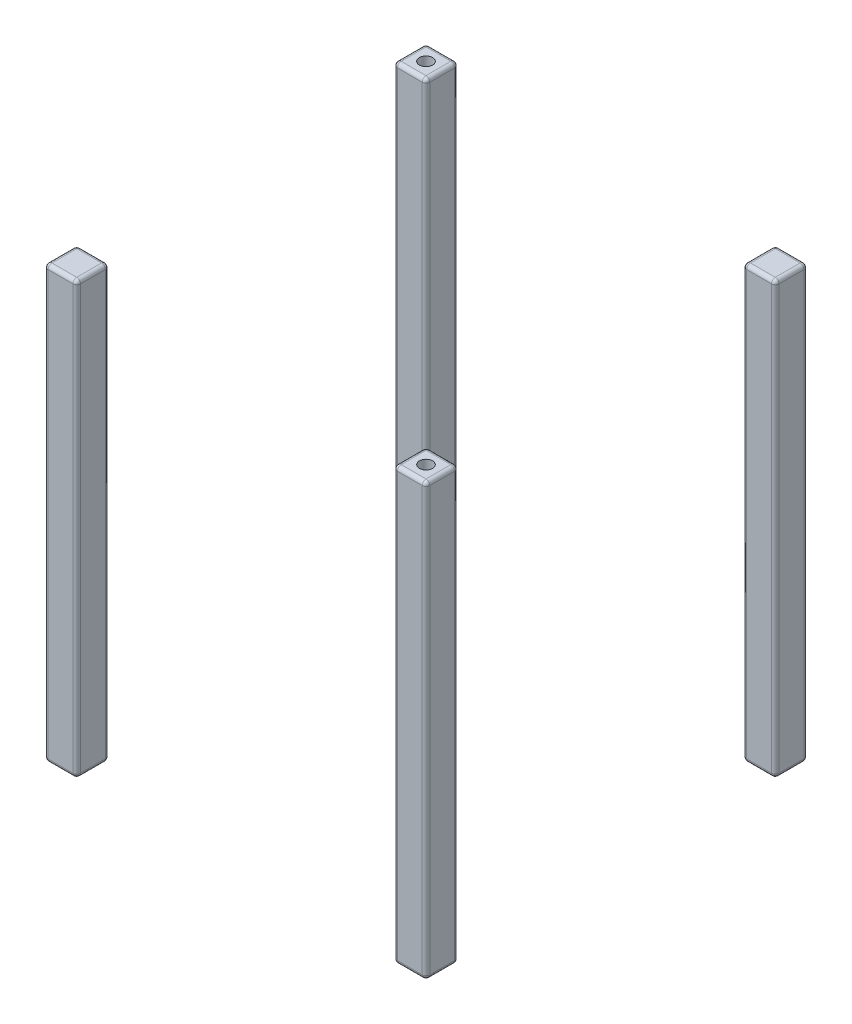
SolidWorks part; units mm, degrees
ref_plane "Front Plane" through (0, 0, 0) normal (0, 0, 1) x (1, 0, 0)
ref_plane "Top Plane" through (0, 0, 0) normal (0, 1, 0) x (1, 0, 0)
ref_plane "Right Plane" through (0, 0, 0) normal (1, 0, 0) x (0, 0, -1)
sketch "Sketch1" plane through (0, 0, 0) normal (0, 1, 0) x (1, 0, 0)
  line L1 (-45.75, 45.75) -> (45.75, 45.75) construction
  line L2 (-45.75, 45.75) -> (-45.75, -45.75) construction
  line L3 (-45.75, -45.75) -> (45.75, -45.75) construction
  line L4 (45.75, 45.75) -> (45.75, -45.75) construction
  line L5 (-49, 50) -> (-41.5, 50)
  line L6 (-50, 49) -> (-50, 41.5)
  line L7 (-50, 41.5) -> (-41.5, 41.5)
  line L8 (-41.5, 50) -> (-41.5, 41.5)
  line L9 (-50, -41.5) -> (-41.5, -41.5)
  line L10 (-50, -41.5) -> (-50, -49)
  line L11 (-49, -50) -> (-41.5, -50)
  line L12 (-41.5, -41.5) -> (-41.5, -50)
  line L13 (41.5, -41.5) -> (50, -41.5)
  line L14 (41.5, -41.5) -> (41.5, -50)
  line L15 (41.5, -50) -> (49, -50)
  line L16 (50, -41.5) -> (50, -49)
  line L17 (41.5, 50) -> (49, 50)
  line L18 (41.5, 50) -> (41.5, 41.5)
  line L19 (41.5, 41.5) -> (50, 41.5)
  line L20 (50, 49) -> (50, 41.5)
  arc A0 (49, 50) -> (50, 49) centre (49, 49) cw
  arc A1 (-49, 50) -> (-50, 49) centre (-49, 49) ccw
  arc A2 (49, -50) -> (50, -49) centre (49, -49) ccw
  arc A3 (-50, -49) -> (-49, -50) centre (-49, -49) ccw
  point P4 (0, 45.75)
  point P5 (-45.75, 0)
  point P22 (-41.5, 45.75)
  point P23 (-45.75, 41.5)
  point P24 (41.5, -45.75)
  point P25 (0, 0)
  point P26 (45.75, -41.5)
  point P27 (0, 0)
  point P28 (0, 0)
  point P38 (-57.9152, -57.9152)
  point P39 (57.5007, 57.5007)
  point P40 (-59.6164, 59.6164)
  point P41 (0, 0)
  point P42 (-44.25, -43.75)
  dimension "D2" = 1
  dimension "D1" = 8.5
  dimension "D3" = 4.25
  dimension "D4" = 100
extrude "Boss-Extrude1" add sketch "Sketch1" along normal blind 113
fillet "Fillet1" radius 1 13 edges at (-45.25, 0, 50) (-49.7071, 0, 49.7071) (-50, 113, 45.25) (-49.7071, 113, 49.7071) (-41.5, 56.5, 41.5) (-45.75, 113, 41.5) (-50, 56.5, 41.5) (-45.75, 0, 41.5) (-41.5, 0, 45.75) (-50, 0, 45.25) (-41.5, 56.5, 50) (-41.5, 113, 45.75) (-45.25, 113, 50)
fillet "Fillet2" radius 1 13 edges at (41.5, 56.5, 50) (41.5, 56.5, 41.5) (45.25, 0, 50) (49.7071, 0, 49.7071) (45.75, 0, 41.5) (41.5, 0, 45.75) (45.75, 113, 41.5) (49.7071, 113, 49.7071) (45.25, 113, 50) (41.5, 113, 45.75) (50, 113, 45.25) (50, 56.5, 41.5) (50, 0, 45.25)
fillet "Fillet3" radius 1 13 edges at (-41.5, 56.5, -50) (-50, 56.5, -41.5) (-41.5, 56.5, -41.5) (-45.75, 113, -41.5) (-50, 113, -45.25) (-49.7071, 113, -49.7071) (-45.25, 113, -50) (-41.5, 113, -45.75) (-45.75, 0, -41.5) (-50, 0, -45.25) (-49.7071, 0, -49.7071) (-45.25, 0, -50) (-41.5, 0, -45.75)
fillet "Fillet4" radius 1 13 edges at (41.5, 56.5, -41.5) (50, 56.5, -41.5) (41.5, 56.5, -50) (45.25, 113, -50) (49.7071, 113, -49.7071) (50, 113, -45.25) (45.75, 113, -41.5) (41.5, 113, -45.75) (45.25, 0, -50) (49.7071, 0, -49.7071) (50, 0, -45.25) (45.75, 0, -41.5) (41.5, 0, -45.75)
hole_wizard "#8-32 Tapped Hole1" positions "Sketch2" profile "Sketch3" tap size "#8-32" standard "ANSI Inch"
sketch "Sketch2" plane through (0, 113, 0) normal (0, 1, 0) x (1, 0, 0)
  line L0 (-49, 50) -> (-42.5, 50) construction
  line L1 (-50, 42.5) -> (-50, 49) construction
  line L2 (50, -42.5) -> (50, -49) construction
  line L3 (49, -50) -> (42.5, -50) construction
  point P0 (-45.75, 45.75)
  point P2 (45.75, -45.75)
  dimension "D1" = 4.25
  dimension "D2" = 4.25
  dimension "D3" = 4.25
  dimension "D4" = 4.25
cosmetic thread "Hole Thread1" parameters "D1"=3.048, "D2"=4.1656
cosmetic thread "Hole Thread2" parameters "D1"=3.048, "D2"=4.1656
sketch "Sketch3" plane through (-45.75, 113, -45.75) normal (1, 0, 0) x (0, 0, 1)
  line L0 (0, 0) -> (0, 12.2138)
  line L1 (0, 12.2138) -> (1.7272, 11.176)
  line L2 (1.7272, 11.176) -> (1.7272, 0)
  line L5 (1.7272, 0) -> (0, 0)
  line L10 (0, 12.2138) -> (-1.7272, 11.176) construction
  line L11 (0, -6.35) -> (0, 107.95) construction
  dimension "Tap Drill Dia." = 3.4544
  dimension "Tap Drill Depth" = 11.176
  dimension "Drill Angle" = 118
hole_wizard "#8-32 Tapped Hole2" positions "Sketch4" profile "Sketch5" tap size "#8-32" standard "ANSI Inch"
sketch "Sketch4" plane through (0, 0, 0) normal (0, -1, 0) x (-1, 0, 0)
  line L0 (49, -50) -> (42.5, -50) construction
  line L1 (50, -42.5) -> (50, -49) construction
  line L2 (-49, 50) -> (-42.5, 50) construction
  line L3 (-50, 42.5) -> (-50, 49) construction
  point P0 (45.75, -45.75)
  point P2 (-45.75, 45.75)
  dimension "D1" = 4.25
  dimension "D2" = 4.25
  dimension "D3" = 4.25
  dimension "D4" = 4.25
sketch "Sketch5" plane through (-45.75, 0, 45.75) normal (1, 0, 0) x (0, 0, -1)
  line L0 (0, 0) -> (0, 12.2138)
  line L1 (0, 12.2138) -> (1.7272, 11.176)
  line L2 (1.7272, 11.176) -> (1.7272, 0)
  line L5 (1.7272, 0) -> (0, 0)
  line L10 (0, 12.2138) -> (-1.7272, 11.176) construction
  line L11 (0, -6.35) -> (0, 107.95) construction
  dimension "Tap Drill Dia." = 3.4544
  dimension "Tap Drill Depth" = 11.176
  dimension "Drill Angle" = 118
cosmetic thread "Hole Thread3" parameters "D1"=3.048, "D2"=4.1656
cosmetic thread "Hole Thread4" parameters "D1"=3.048, "D2"=4.1656
